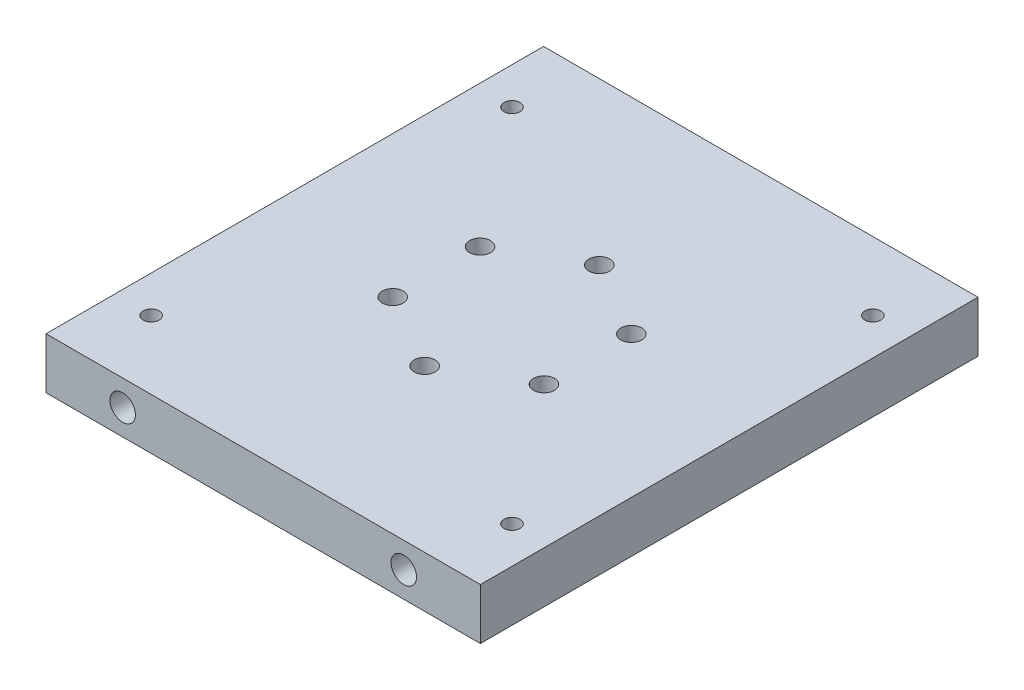
SolidWorks part; units mm, degrees
material "6061-T6 (SS)"
ref_plane "Front Plane" through (0, 0, 0) normal (0, 0, 1) x (1, 0, 0)
ref_plane "Top Plane" through (0, 0, 0) normal (0, 1, 0) x (1, 0, 0)
ref_plane "Right Plane" through (0, 0, 0) normal (1, 0, 0) x (0, 0, -1)
sketch "Sketch1" plane through (0, 0, 0) normal (0, 0, 1) x (1, 0, 0)
  line L1 (0, 0) -> (107.95, 0)
  line L2 (0, 0) -> (0, -12.7)
  line L3 (0, -12.7) -> (107.95, -12.7)
  line L4 (107.95, 0) -> (107.95, -12.7)
  line L5 (0, 0) -> (107.95, -12.7) construction
  line L6 (0, -12.7) -> (107.95, 0) construction
  point P5 (53.975, -6.35)
  dimension "D1" = 12.7
  dimension "D2" = 107.95
extrude "Boss-Extrude1" add sketch "Sketch1" along normal blind 123.65
sketch "Sketch2" plane through (0, 0, 123.65) normal (0, 0, 1) x (1, 0, 0)
  line L0 (0, -6.35) -> (107.95, -6.35) construction
  line L1 (0, 0) -> (0, -12.7) construction
  line L2 (107.95, -12.7) -> (107.95, 0) construction
  circle A0 centre (19.05, -6.35) radius 3.175
  circle A1 centre (88.9, -6.35) radius 3.175
  dimension "D1" = 6.35
  dimension "D2" = 6.35
  dimension "D3" = 19.05
  dimension "D4" = 19.05
extrude "Cut-Extrude1" cut sketch "Sketch2" against normal blind 25.4
ref_plane "Plane1" through (0, 0, 61.825) normal (0, 0, 1) x (1, 0, 0)
mirror "Mirror1" about plane through (0, 0, 61.825) normal (0, 0, 1) of "Cut-Extrude1"
sketch "Sketch6" plane through (0, -12.7, 0) normal (0, -1, 0) x (1, 0, 0)
  circle A0 centre (53.9767, 83.525) radius 2.6 construction
  circle A1 centre (35.1831, 72.6765) radius 2.6 construction
  circle A2 centre (35.1814, 50.9765) radius 2.6 construction
  circle A3 centre (72.7686, 72.6735) radius 2.6 construction
  circle A4 centre (72.7669, 50.9735) radius 2.6 construction
  circle A5 centre (53.9733, 40.125) radius 2.6 construction
  circle A6 centre (9.13, 16.98) radius 1.985 construction
  circle A7 centre (98.82, 16.98) radius 1.985 construction
  circle A8 centre (9.13, 106.67) radius 1.985 construction
  circle A9 centre (98.82, 106.67) radius 1.985 construction
  circle A10 centre (53.9767, 83.525) radius 2.6
  circle A11 centre (35.1831, 72.6765) radius 2.6
  circle A12 centre (35.1814, 50.9765) radius 2.6
  circle A13 centre (72.7686, 72.6735) radius 2.6
  circle A14 centre (72.7669, 50.9735) radius 2.6
  circle A15 centre (53.9733, 40.125) radius 2.6
  circle A16 centre (9.13, 16.98) radius 1.985
  circle A17 centre (98.82, 16.98) radius 1.985
  circle A18 centre (9.13, 106.67) radius 1.985
  circle A19 centre (98.82, 106.67) radius 1.985
extrude "Cut-Extrude2" cut sketch "Sketch6" against normal up to surface (12.7 mm away) up to face at (53.975, 0, 61.825)
